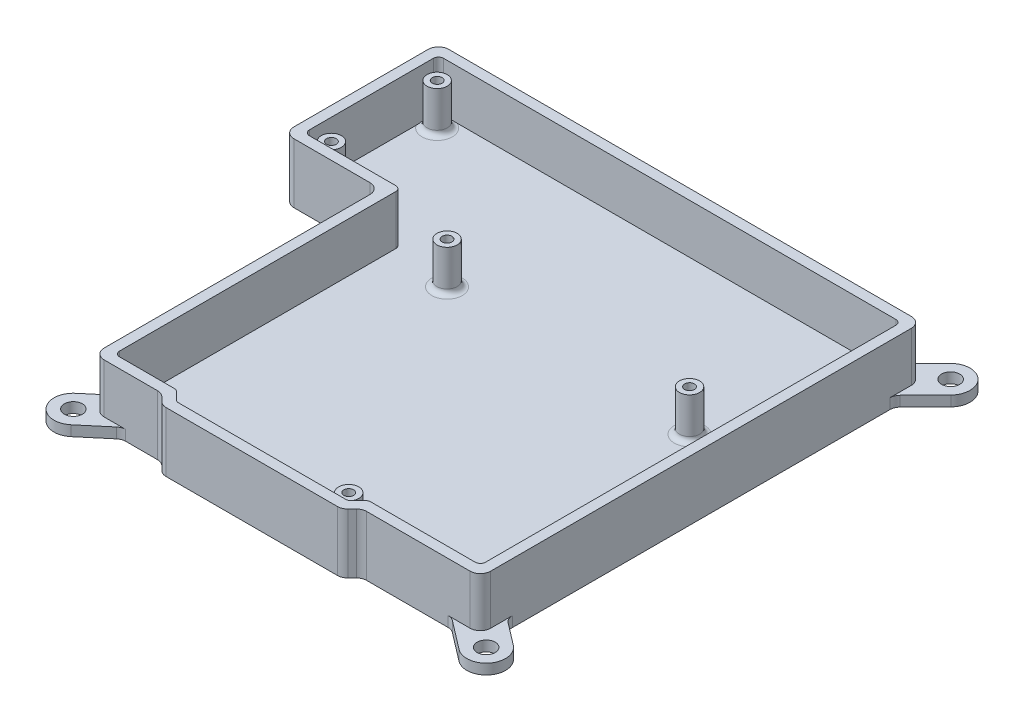
SolidWorks part; units mm, degrees
ref_plane "Alzado" through (0, 0, 0) normal (0, 0, 1) x (1, 0, 0)
ref_plane "Planta" through (0, 0, 0) normal (0, 1, 0) x (1, 0, 0)
ref_plane "Vista lateral" through (0, 0, 0) normal (1, 0, 0) x (0, 0, -1)
sketch "Croquis1" plane through (0, 0, 0) normal (0, 1, 0) x (1, 0, 0)
  line B0 (-18.7249, 81.5) -> (70.898, 81.5)
  line B1 (70.898, 81.5) -> (70.898, 0)
  line B2 (70.898, 0) -> (49.2071, 0)
  line B3 (49.2071, 0) -> (47.2071, -2)
  line B4 (47.2071, -2) -> (14, -2)
  line B5 (14, -2) -> (12, 0)
  line B6 (12, 0) -> (0, 0)
  line B7 (0, 0) -> (0, 55.5)
  line B8 (0, 55.5) -> (-18.7249, 55.5)
  line B9 (-18.7249, 55.5) -> (-18.7249, 81.5)
  circle B10 centre (-16.2249, 78.75) radius 0.95
  circle B11 centre (-16.2249, 58.25) radius 0.95
  circle B12 centre (11.37, 53.07) radius 0.95
  circle B13 centre (59.63, 51.8) radius 0.95
  circle B14 centre (44.39, 1) radius 0.95
  circle B15 centre (75.675, -3.65) radius 1.75
  circle B16 centre (75.675, 86.35) radius 1.75
  circle B17 centre (-24.325, 86.35) radius 1.75
  circle B18 centre (-4.325, -3.65) radius 1.75
sketch_block_instance "Bloque1-1"
sketch_block "Bloque1"
sketch "Croquis2" plane through (0, 0, 0) normal (0, 1, 0) x (1, 0, 0)
  line L0 (-2, -0.7077) -> (-2, 3.2191) construction
  line L1 (-2, 3.2191) -> (-2, 53.5)
  line L2 (-2, -2) -> (-2, 53.5) construction
  line L3 (-2, -1.6879) -> (-2, -0.7077) construction
  line L4 (-2.9876, -2.5213) -> (-2, -1.6879) construction
  line L16 (70.898, 81.5) -> (70.898, 0) construction
  line L17 (70.898, 0) -> (49.2071, 0) construction
  line L18 (49.2071, 0) -> (47.2071, -2) construction
  line L19 (47.2071, -2) -> (14, -2) construction
  line L20 (14, -2) -> (12, 0) construction
  line L21 (12, 0) -> (0, 0) construction
  line L22 (0, 0) -> (0, 55.5) construction
  line L23 (0, 55.5) -> (-18.7249, 55.5) construction
  line L24 (-18.7249, 81.5) -> (70.898, 81.5) construction
  line L25 (-18.7249, 55.5) -> (-18.7249, 81.5) construction
  line L26 (70.898, 81.5) -> (70.898, 0) construction
  line L27 (70.898, 0) -> (49.2071, 0) construction
  line L28 (49.2071, 0) -> (47.2071, -2)
  line L29 (47.2071, -2) -> (14, -2)
  line L30 (14, -2) -> (12, 0)
  line L31 (12, 0) -> (0, 0) construction
  line L32 (0, 0) -> (0, 55.5)
  line L33 (0, 55.5) -> (-18.7249, 55.5)
  line L34 (-18.7249, 81.5) -> (70.898, 81.5) construction
  line L35 (-18.7249, 55.5) -> (-18.7249, 81.5) construction
  line L36 (-14.6832, 83.5) -> (67.6044, 83.5)
  line L37 (72.898, 78.1866) -> (72.898, 3.1912)
  line L38 (72.898, -2) -> (72.3075, -2) construction
  line L39 (50.0355, -2) -> (48.0355, -4)
  line L40 (48.0355, -4) -> (13.1716, -4)
  line L41 (13.1716, -4) -> (11.1716, -2)
  line L42 (11.1716, -2) -> (3.4445, -2)
  line L43 (-2, -2) -> (-2, -1.6879) construction
  line L44 (-2, 53.5) -> (-20.7249, 53.5)
  line L45 (-20.7249, 53.5) -> (-20.7249, 78.7172)
  line L46 (-26.6526, 83.4098) -> (-20.7249, 78.7172)
  line L47 (-21.9974, 89.2902) -> (-14.6832, 83.5)
  line L48 (-24.325, 86.35) -> (-22.9529, 85.2638) construction
  line L49 (-4.325, -3.65) -> (-2.9876, -2.5213) construction
  line L50 (75.675, -3.65) -> (74.2845, -2.5875) construction
  line L51 (70.898, 81.5) -> (73.0435, 83.6783) construction
  line L52 (73.0033, 88.9815) -> (67.6044, 83.5)
  line L53 (78.3467, 83.7185) -> (72.898, 78.1866)
  line L54 (77.9518, -0.6703) -> (72.898, 3.1912)
  line L55 (73.3982, -6.6297) -> (67.339, -2)
  line L56 (-1.9064, -6.5158) -> (3.4445, -2)
  line L57 (-6.7436, -0.7842) -> (-2, 3.2191)
  line L58 (-20.7249, 83.5) -> (-14.6832, 83.5) construction
  line L59 (-20.7249, 83.5) -> (72.898, 83.5) construction
  line L60 (-22.9529, 85.2638) -> (-21.3848, 84.0224) construction
  line L61 (-21.3848, 84.0224) -> (-20.7249, 83.5) construction
  line L62 (-20.7249, 78.7172) -> (-20.7249, 83.5) construction
  line L63 (-20.7249, 53.5) -> (-20.7249, 83.5) construction
  line L64 (67.6044, 83.5) -> (72.8679, 83.5) construction
  line L65 (72.8679, 83.5) -> (72.898, 83.5)
  line L66 (73.0435, 83.6783) -> (74.447, 85.1032) construction
  line L67 (74.447, 85.1032) -> (75.675, 86.35) construction
  line L68 (72.898, 83.5) -> (72.898, 78.1866) construction
  line L69 (72.898, 83.5) -> (72.898, -2) construction
  line L70 (72.898, 3.1912) -> (72.898, -1.1299) construction
  line L71 (72.898, -1.5282) -> (72.898, -2) construction
  line L72 (74.2845, -2.5875) -> (72.898, -1.5282) construction
  line L73 (72.898, -1.5282) -> (72.6953, -1.3732) construction
  line L74 (72.3075, -2) -> (67.339, -2) construction
  line L75 (67.339, -2) -> (50.0355, -2)
  line L76 (72.898, -2) -> (50.0355, -2) construction
  line L77 (72.6953, -1.3732) -> (70.898, 0) construction
  line L78 (72.898, -1.1299) -> (72.898, -1.5282) construction
  line L79 (3.4445, -2) -> (-0.9575, -2) construction
  line L80 (-0.9575, -2) -> (-2, -2) construction
  line L81 (11.1716, -2) -> (-2, -2) construction
  line L82 (-2, -1.6879) -> (-1.4592, -1.2314) construction
  line L83 (-1.4592, -1.2314) -> (0, 0) construction
  arc A0 (-2, -0.7077) -> (-6.7436, -0.7842) centre (-4.325, -3.65) ccw construction
  circle A4 centre (75.675, 86.35) radius 1.75 construction
  circle A5 centre (75.675, -3.65) radius 1.75 construction
  circle A6 centre (-4.325, -3.65) radius 1.75 construction
  circle A7 centre (-24.325, 86.35) radius 1.75 construction
  circle A8 centre (75.675, 86.35) radius 1.75
  circle A9 centre (75.675, -3.65) radius 1.75
  circle A10 centre (-4.325, -3.65) radius 1.75
  circle A11 centre (-24.325, 86.35) radius 1.75
  arc A12 (-21.9974, 89.2902) -> (-26.6526, 83.4098) centre (-24.325, 86.35) ccw
  arc A13 (-0.9575, -2) -> (-1.4592, -1.2314) centre (-4.325, -3.65) ccw construction
  arc A14 (72.898, -1.1299) -> (72.6953, -1.3732) centre (75.675, -3.65) ccw construction
  arc A15 (78.3467, 83.7185) -> (73.0033, 88.9815) centre (75.675, 86.35) ccw
  arc A16 (-21.3848, 84.0224) -> (-21.9974, 89.2902) centre (-24.325, 86.35) ccw construction
  circle A17 centre (-24.325, 86.35) radius 3.75 construction
  arc A18 (-26.6526, 83.4098) -> (-21.3848, 84.0224) centre (-24.325, 86.35) ccw construction
  arc A19 (73.0033, 88.9815) -> (73.0435, 83.6783) centre (75.675, 86.35) ccw construction
  circle A20 centre (75.675, 86.35) radius 3.75 construction
  arc A21 (73.0435, 83.6783) -> (78.3467, 83.7185) centre (75.675, 86.35) ccw construction
  arc A22 (77.9518, -0.6703) -> (72.898, -1.1299) centre (75.675, -3.65) ccw construction
  circle A23 centre (75.675, -3.65) radius 3.75 construction
  arc A24 (72.3075, -2) -> (73.3982, -6.6297) centre (75.675, -3.65) ccw construction
  arc A25 (73.3982, -6.6297) -> (77.9518, -0.6703) centre (75.675, -3.65) ccw
  arc A26 (72.6953, -1.3732) -> (72.3075, -2) centre (75.675, -3.65) ccw construction
  arc A27 (-1.9064, -6.5158) -> (-0.9575, -2) centre (-4.325, -3.65) ccw construction
  circle A28 centre (-4.325, -3.65) radius 3.75 construction
  arc A29 (-1.4592, -1.2314) -> (-2, -0.7077) centre (-4.325, -3.65) ccw construction
  arc A30 (-6.7436, -0.7842) -> (-1.9064, -6.5158) centre (-4.325, -3.65) ccw
  dimension "D1" = 2
extrude "Saliente-Extruir1" add sketch "Croquis2" along normal blind 2 contours L57 A30 L56 L42 L41 L40 L39 L75 L55 A25 L54 L37 L53 A15 L52 L36 L47 A12 L46 L45 L44 L1 A8 A9 A10 A11 region at (31.6038, 0, -42.5823)
sketch "Croquis3" plane through (0, 2, 0) normal (0, 1, 0) x (1, 0, 0)
  line L0 (70.898, 81.5) -> (70.898, 0) construction
  line L1 (49.2071, 0) -> (47.2071, -2) construction
  line L2 (70.898, 0) -> (49.2071, 0) construction
  line L3 (12, 0) -> (0, 0) construction
  line L4 (14, -2) -> (12, 0) construction
  line L5 (47.2071, -2) -> (14, -2) construction
  line L6 (0, 0) -> (0, 55.5) construction
  line L7 (0, 55.5) -> (-18.7249, 55.5) construction
  line L8 (-18.7249, 81.5) -> (70.898, 81.5) construction
  line L9 (-18.7249, 55.5) -> (-18.7249, 81.5) construction
  line L10 (70.898, 81.5) -> (70.898, 0)
  line L11 (49.2071, 0) -> (47.2071, -2)
  line L12 (70.898, 0) -> (49.2071, 0)
  line L13 (12, 0) -> (0, 0)
  line L14 (14, -2) -> (12, 0)
  line L15 (47.2071, -2) -> (14, -2)
  line L16 (0, 0) -> (0, 55.5)
  line L17 (0, 55.5) -> (-18.7249, 55.5)
  line L18 (-18.7249, 81.5) -> (70.898, 81.5)
  line L19 (-18.7249, 55.5) -> (-18.7249, 81.5)
  line L20 (-20.7249, 83.5) -> (72.898, 83.5)
  line L21 (72.898, 83.5) -> (72.898, -2)
  line L22 (72.898, -2) -> (50.0355, -2)
  line L23 (50.0355, -2) -> (48.0355, -4)
  line L24 (48.0355, -4) -> (13.1716, -4)
  line L25 (13.1716, -4) -> (11.1716, -2)
  line L26 (11.1716, -2) -> (-2, -2)
  line L27 (-2, -2) -> (-2, 53.5)
  line L28 (-2, 53.5) -> (-20.7249, 53.5)
  line L29 (-20.7249, 53.5) -> (-20.7249, 83.5)
  dimension "D1" = 2
extrude "Saliente-Extruir2" add sketch "Croquis3" along normal blind 9.58
sketch "Croquis4" plane through (0, 2, 0) normal (0, 1, 0) x (1, 0, 0)
  circle A0 centre (44.39, 1) radius 0.95 construction
  circle A1 centre (59.63, 51.8) radius 0.95 construction
  circle A2 centre (11.37, 53.07) radius 0.95 construction
  circle A3 centre (-16.2249, 58.25) radius 0.95 construction
  circle A4 centre (-16.2249, 78.75) radius 0.95 construction
  circle A5 centre (44.39, 1) radius 0.95
  circle A6 centre (59.63, 51.8) radius 0.95
  circle A7 centre (11.37, 53.07) radius 0.95
  circle A8 centre (-16.2249, 58.25) radius 0.95
  circle A9 centre (-16.2249, 78.75) radius 0.95
  circle A10 centre (-16.2249, 78.75) radius 1.95
  circle A11 centre (-16.2249, 58.25) radius 1.95
  circle A12 centre (11.37, 53.07) radius 1.95
  circle A13 centre (59.63, 51.8) radius 1.95
  circle A14 centre (44.39, 1) radius 1.95
  dimension "D1" = 1
  dimension "D2" = 1
extrude "Saliente-Extruir3" add sketch "Croquis4" along normal blind 8
fillet "Redondeo2" radius 2 18 edges at (72.898, 6.79, 2) (-14.6832, 1, -83.5) (-20.7249, 6.79, -83.5) (-20.7249, 1, -78.7172) (-20.7249, 5.79, -53.5) (-2, 5.79, -53.5) (-2, 1, -3.2191) (-2, 6.79, 2) (3.4445, 1, 2) (11.1716, 5.79, 2) (13.1716, 5.79, 4) (50.0355, 5.79, 2) (48.0355, 5.79, 4) (67.6044, 1, -83.5) (72.898, 6.79, -83.5) (72.898, 1, -78.1866) (72.898, 1, -3.1912) (67.339, 1, 2)
fillet "Redondeo3" radius 1 10 edges at (70.898, 6.79, -81.5) (70.898, 6.79, 0) (49.2071, 6.79, 0) (47.2071, 6.79, 2) (14, 6.79, 2) (12, 6.79, 0) (0, 6.79, 0) (0, 6.79, -55.5) (-18.7249, 6.79, -55.5) (-18.7249, 6.79, -81.5)
fillet "Redondeo4" radius 1 5 edges at (44.39, 2, 0.95) (59.63, 2, -49.85) (-16.2249, 2, -76.8) (-16.2249, 2, -56.3) (11.37, 2, -51.12)
